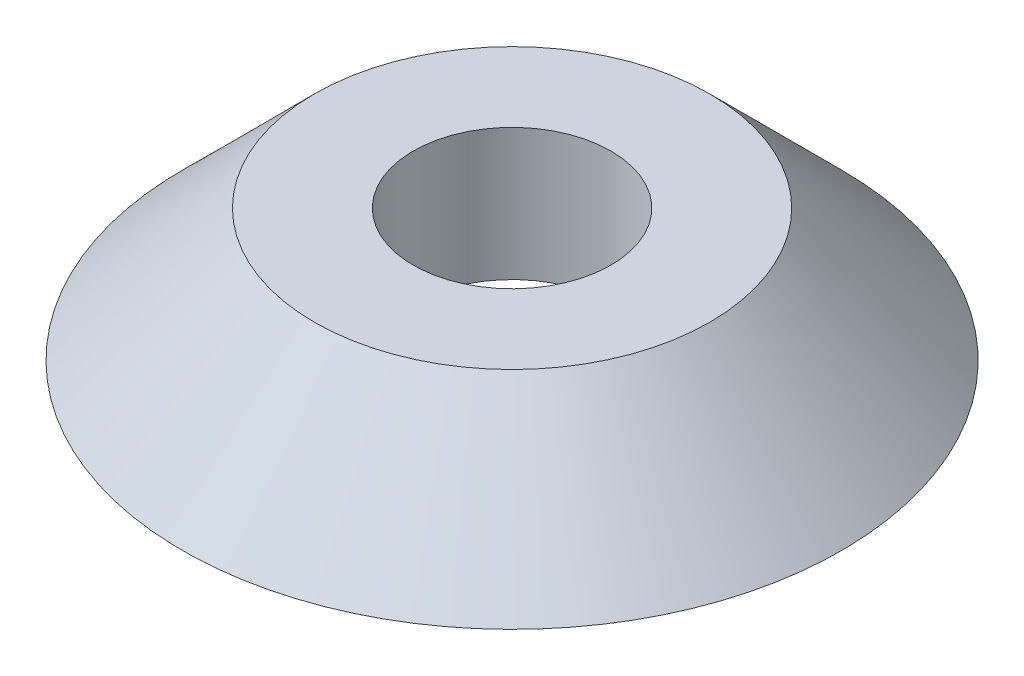
SolidWorks part; units mm, degrees
ref_plane "Front Plane" through (0, 0, 0) normal (0, 0, 1) x (1, 0, 0)
ref_plane "Top Plane" through (0, 0, 0) normal (0, 1, 0) x (1, 0, 0)
ref_plane "Right Plane" through (0, 0, 0) normal (1, 0, 0) x (0, 0, -1)
sketch "Sketch1" plane through (0, 0, 0) normal (0, 0, 1) x (1, 0, 0)
  line L0 (0, -1000.6938) -> (0, 48999.3062) construction
  line L1 (9.525, 0) -> (31.75, 0)
  line L2 (31.75, 0) -> (19.05, 12.7)
  line L3 (19.05, 12.7) -> (9.525, 12.7)
  line L4 (9.525, 12.7) -> (0, 12.7) construction
  line L5 (9.525, 12.7) -> (9.525, 0)
  line L6 (0, 0) -> (9.525, 0) construction
  dimension "D1" = 45
  dimension "D2" = 12.7
  dimension "D3" = 38.1
  dimension "D4" = 19.05
revolve "Revolve1" add sketch "Sketch1" angle 360 about L0
ref_axis "Axis1" through (0, 12.7, 0) along (0, -1, 0)
ref_plane "Plane1" through (0, 25.4, 0) normal (0, 1, 0) x (1, 0, 0)
ref_axis "Axis2" through (34.925, 25.4, 0) along (-1, 0, 0)
